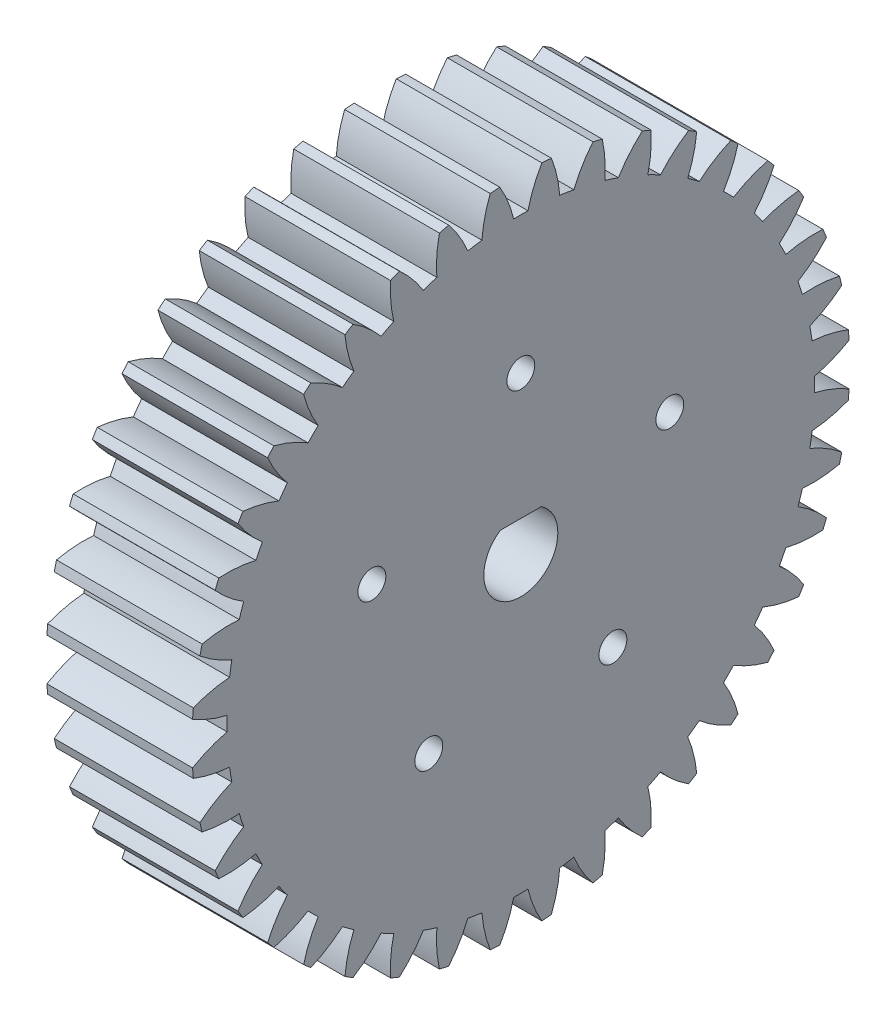
SolidWorks part; units mm, degrees
ref_plane "Plane1" through (0, 0, 0) normal (0, 0, 1) x (1, 0, 0)
ref_plane "Plane2" through (0, 0, 0) normal (0, 1, 0) x (1, 0, 0)
ref_plane "Plane3" through (0, 0, 0) normal (1, 0, 0) x (0, 0, -1)
sketch "HoldingSke" plane through (0, 0, 0) normal (0, 1, 0) x (1, 0, 0)
  line L0 (0, 0) -> (389.1506, -326.5361)
  line L1 (-15, 0) -> (100, 0) construction
  line L2 (0, 0) -> (-2.1039, 2.3779)
  line L3 (0, 0) -> (-11.863, 4.5341)
  line L4 (0, 0) -> (6.6156, 5.5511)
  line L5 (0, 0) -> (-47.5972, -17.7524)
  line L6 (0, 0) -> (-9.7909, -6.6059)
  line L7 (-2.1039, 2.3779) -> (8.8308, 51.9871)
  line L8 (-76.2, 54.61) -> (-75.184, 54.61)
  line L9 (-71.009, 38.7566) -> (-53.1078, 45.2721)
  line L10 (-76.2, 71.12) -> (104.1128, 71.12)
  line L11 (0, 0) -> (-11.811, 0)
  line L12 (-76.2, 101.6) -> (-76.1492, 101.6)
  line L13 (24.9733, 27.94) -> (52.9518, 28.4284)
  line L14 (24.9733, 27.94) -> (25.0241, 27.9398)
  line L15 (24.9733, 27.94) -> (100.4021, 29.52)
  circle A0 centre (0, 0) radius 0.3969
  circle A1 centre (0, 0) radius 23.8252
  circle A2 centre (0, 0) radius 38.1
  circle A3 centre (0, 0) radius 0.3969
  dimension "MHD" = 47.6504
  dimension "Hub_dia" = 76.2
  dimension "Bore" = 0.7937
  dimension "MBD" = 0.7937
  dimension "Num_teeth" = 40
  dimension "Pitch_radius" = 180.3128
  dimension "Pitch" = 508
  dimension "Width" = 11.811
  dimension "Overall_len" = 50.8
  dimension "Show_teeth" = 40
  dimension "Thickness" = 11.811
  dimension "OAL" = 50.8001
  dimension "T_dim" = 1.016
  dimension "Ap" = 20
  dimension "H" = 19.05
  dimension "Backlash" = 0.0508
  dimension "Addendum_fac" = 1
  dimension "Dedendum_fac" = 1.2
  dimension "Clearance_fac" = 0.2
  dimension "Dedendum_add" = 0.0508
sketch "BasProSke" plane through (0, 0, 0) normal (0, 1, 0) x (1, 0, 0)
  line L0 (-10, 0) -> (60, 0) construction
  line L1 (0, 0) -> (0, 26.67)
  line L2 (0, 0) -> (11.811, 0)
  line L3 (11.811, 0) -> (11.811, 26.67)
  line L4 (11.811, 26.67) -> (0, 26.67)
  dimension "Diameter" = 53.34
  dimension "Thickness" = 11.811
revolve "Base-Revolve" add sketch "BasProSke" angle 360 about L0
sketch "TooCutSke" plane through (0, 0, 0) normal (1, 0, 0) x (0, 0, -1)
  line L1 (0, 0) -> (0, 107) construction
  line L2 (0, 0) -> (-1.0861, 25.3768) construction
  line L3 (0, 0) -> (-3.9832, 50.611) construction
  line L4 (-1.0861, 25.3768) -> (-1.9916, 25.3055) construction
  arc A0 (0.5773, 23.8182) -> (-0.5773, 23.8182) centre (0, 0) ccw
  arc A1 (1.7213, 26.6399) -> (-1.7213, 26.6399) centre (0, 0) ccw
  circle A2 centre (0, 0) radius 25.4 construction
  circle A3 centre (0, 0) radius 23.8682 construction
  arc A4 (-0.5773, 23.8182) -> (-1.7213, 26.6399) centre (-10.4586, 21.4548) ccw
  arc A5 (1.7213, 26.6399) -> (0.5773, 23.8182) centre (10.4586, 21.4548) ccw
  dimension "Root_dia" = 47.6504
  dimension "Overcut_dia" = 53.3908
  dimension "Pitch_dia" = 50.8
  dimension "Base_dia" = 47.7364
  dimension "Flank_rad" = 10.16
  dimension "Half_ang" = 4.5
  dimension "Half_CT" = 0.9083
extrude "ToothCut" cut sketch "TooCutSke" along normal through all
fillet "Breaks" [suppressed] radius 0.0254 tangent propagation no
fillet "RootFillets" [suppressed] radius 0.3048
pattern_circular "TeethCuts" count 40 every 9 about axis through (-10, 0, 0) along (1, 0, 0) of "ToothCut", "RootFillets", "Breaks"
sketch "HubNeaOneSke" plane through (0, 0, 0) normal (-1, 0, 0) x (0, 0, 1)
  circle A0 centre (0, 0) radius 23.8252
  dimension "Diameter" = 47.6504
extrude "HubNearOne" [suppressed] add sketch "HubNeaOneSke" along normal blind 38.9891
sketch "HubNeaBotSke" plane through (0, 0, 0) normal (-1, 0, 0) x (0, 0, 1)
  circle A0 centre (0, 0) radius 23.8252
  dimension "Diameter" = 47.6504
extrude "HubNearBoth" [suppressed] add sketch "HubNeaBotSke" along normal blind 19.4945
ref_plane "FarPln" through (11.811, 0, 0) normal (1, 0, 0) x (0, 0, -1)
sketch "HubFarSke" plane through (11.811, 0, 0) normal (1, 0, 0) x (0, 0, -1)
  circle A0 centre (0, 0) radius 23.8252
  dimension "Diameter" = 47.6504
extrude "HubFar" [suppressed] add sketch "HubFarSke" along normal blind 19.4945
sketch "BorSke" plane through (0, 0, 0) normal (1, 0, 0) x (0, 0, -1)
  circle A0 centre (0, 0) radius 0.3969
  dimension "Diameter" = 0.7937
extrude "Bore" cut sketch "BorSke" along normal mid plane 101.6001
sketch "KeySke" plane through (0, 0, 0) normal (1, 0, 0) x (0, 0, -1)
  line L0 (-0.127, 0) -> (-0.127, 0.6191)
  line L1 (-0.127, 0.6191) -> (0.127, 0.6191)
  line L2 (0.127, 0.6191) -> (0.127, 0)
  line L3 (0, 0) -> (0, 34) construction
  line L4 (-0.127, 0) -> (0.127, 0)
  dimension "Offset" = 0.6191
  dimension "Width" = 0.254
extrude "Keyway" [suppressed] cut sketch "KeySke" along normal mid plane 101.6001
pattern_circular "Keyway2" [suppressed] count 2 every 90 about axis through (-10, 0, 0) along (1, 0, 0)
sketch "Sketch3" plane through (11.811, 0, 0) normal (1, 0, 0) x (0, 0, -1)
  line L0 (-1.6583, 2.5) -> (1.6583, 2.5)
  line L1 (0, 0) -> (0, 32.5169) construction
  arc A0 (-1.6583, 2.5) -> (1.6583, 2.5) centre (0, 0) ccw
  circle A1 centre (0, 12.7) radius 1.1303
  circle A2 centre (12.0784, 3.9245) radius 1.1303
  circle A3 centre (7.4649, -10.2745) radius 1.1303
  circle A4 centre (-7.4649, -10.2745) radius 1.1303
  circle A5 centre (-12.0784, 3.9245) radius 1.1303
  point P18 (0, 0)
  dimension "D1" = 6
  dimension "D3" = 2.2606
  dimension "D2" = 2.5
  dimension "D4" = 12.7
  dimension "D5" = 5
extrude "Cut-Extrude1" cut sketch "Sketch3" against normal blind 15.748
equation "' \"Pitch@HoldingSke\" = 4"
equation "' \"Num_teeth@HoldingSke\" = 12"
equation "' \"Ap@HoldingSke\" =  20"
equation "' \"Width@HoldingSke\" = 0.5"
equation "' \"Hub_dia@HoldingSke\"= 1"
equation "' \"Overall_len@HoldingSke\" = 1.0"
equation "' \"Bore@HoldingSke\" = 0.75"
equation "' \"T_dim@HoldingSke\" = 0.85"
equation "' \"Width@KeySke\" = 0.25"
equation "' \"Show_teeth@HoldingSke\" = 13"
equation "' \"Backlash@HoldingSke\" = 0.009"
equation "' \"Addendum_fac@HoldingSke\" = 1.0"
equation "' \"Dedendum_fac@HoldingSke\" = 1.25"
equation "' \"Dedendum_add@HoldingSke\" = 0.00005"
equation "' \"Clearance_fac@HoldingSke\" = 0.25"
equation "' \"Pitch@HoldingSke\" = 0.5"
equation "' \"Num_teeth@HoldingSke\" = 23"
equation "' \"Show_teeth@HoldingSke\" = 23"
equation "' \"Backlash@HoldingSke\" = 0.0375"
equation "\"Overcut_dia@TooCutSke\" = (\"Num_teeth@HoldingSke\" + 2 * \"Addendum_fac@HoldingSke\") / \"Pitch@HoldingSke\" + 0.002"
equation "\"Pitch_dia@TooCutSke\" = \"Num_teeth@HoldingSke\" / \"Pitch@HoldingSke\""
equation "\"Base_dia@TooCutSke\" = \"Num_teeth@HoldingSke\" / \"Pitch@HoldingSke\" * cos((\"Ap@HoldingSke\"  * 3.14159265 / 180))"
equation "\"Root_dia@TooCutSke\" = (\"Num_teeth@HoldingSke\" + 2) / \"Pitch@HoldingSke\" - 2 * (\"Addendum_fac@HoldingSke\" + \"Dedendum_fac@HoldingSke\") / \"Pitch@HoldingSke\" - \"Dedendum_add@HoldingSke\" * 2"
equation "\"Half_ang@TooCutSke\" = 180 / \"Num_teeth@HoldingSke\""
equation "\"Half_CT@TooCutSke\" = \"Num_teeth@HoldingSke\" / \"Pitch@HoldingSke\" * sin((3.14159265 / 2 / \"Num_teeth@HoldingSke\")) / 2 - 7 * \"Backlash@HoldingSke\" / 4"
equation "\"Flank_rad@TooCutSke\" = \"Num_teeth@HoldingSke\" / \"Pitch@HoldingSke\" / 5"
equation "\"Radius@RootFillets\" = \"Clearance_fac@HoldingSke\" / \"Pitch@HoldingSke\" + \"Dedendum_add@HoldingSke\""
equation "\"Break_rad@Breaks\" = 0.02 / \"Pitch@HoldingSke\""
equation "\"Thickness@HoldingSke\" = \"Width@HoldingSke\""
equation "\"OAL@HoldingSke\" = \"Thickness@HoldingSke\""
equation "\"MHD@HoldingSke\" = (\"Num_teeth@HoldingSke\" + 2) / \"Pitch@HoldingSke\" - 2 * (\"Addendum_fac@HoldingSke\" + \"Dedendum_fac@HoldingSke\")  / \"Pitch@HoldingSke\" - \"Dedendum_add@HoldingSke\" * 2"
equation "\"MBD@HoldingSke\" = (\"Num_teeth@HoldingSke\" + 2) / \"Pitch@HoldingSke\" - 2 * (\"Addendum_fac@HoldingSke\" + \"Dedendum_fac@HoldingSke\")  / \"Pitch@HoldingSke\" - \"Dedendum_add@HoldingSke\" * 2 - 0.002"
equation "\"MHD@HoldingSke\" = ((sgn( \"MHD@HoldingSke\" - \"Hub_dia@HoldingSke\" )-1)*( \"MHD@HoldingSke\" - \"Hub_dia@HoldingSke\" ))/-2+ \"Hub_dia@HoldingSke\""
equation "\"MBD@HoldingSke\" = ((sgn( \"MBD@HoldingSke\" - \"Bore@HoldingSke\" )-1)*( \"MBD@HoldingSke\" - \"Bore@HoldingSke\" ))/-2+ \"Bore@HoldingSke\""
equation "\"OAL@HoldingSke\" = ((sgn( \"OAL@HoldingSke\" - \"Overall_len@HoldingSke\" )+1)*( \"OAL@HoldingSke\" - \"Overall_len@HoldingSke\" ))/2 + \"Overall_len@HoldingSke\" + 0.000002"
equation "\"Num_teeth@TeethCuts\" = int( \"Show_teeth@HoldingSke\" ) + 1"
equation "\"Num_teeth@TeethCuts\" = ((sgn( \"Num_teeth@TeethCuts\" - \"Num_teeth@HoldingSke\" )-1)*( \"Num_teeth@TeethCuts\" - \"Num_teeth@HoldingSke\" ))/-2+ \"Num_teeth@HoldingSke\""
equation "\"Num_teeth@TeethCuts\" = ((sgn( \"Num_teeth@TeethCuts\" - 2.0)+1)*( \"Num_teeth@TeethCuts\" - 2.0))/2 +2.0"
equation "\"Angle@TeethCuts\" = 360.0 / \"Num_teeth@HoldingSke\""
equation "\"Diameter@BasProSke\" = (\"Num_teeth@HoldingSke\" + 2 * \"Addendum_fac@HoldingSke\") / \"Pitch@HoldingSke\""
equation "\"Thickness@BasProSke\"  = \"Thickness@HoldingSke\""
equation "' \"Fillet_rad@BasProSke\" =  \"Thickness@HoldingSke\" * 0.05"
equation "\"MHD@HoldingSke\" = ((sgn( \"MHD@HoldingSke\" - \"Root_dia@TooCutSke\" )-1)*( \"MHD@HoldingSke\" - \"Root_dia@TooCutSke\" ))/-2+ \"Root_dia@TooCutSke\""
equation "\"Diameter@HubNeaOneSke\" = \"MHD@HoldingSke\""
equation "\"Length@HubNearOne\" = \"OAL@HoldingSke\" - \"Thickness@BasProSke\""
equation "\"Diameter@HubNeaBotSke\" = \"MHD@HoldingSke\""
equation "\"Length@HubNearBoth\" = ( \"OAL@HoldingSke\" - \"Thickness@BasProSke\" ) / 2.0"
equation "\"Thickness@FarPln\" = \"Thickness@BasProSke\""
equation "\"Diameter@HubFarSke\" = \"MHD@HoldingSke\""
equation "\"Length@HubFar\" = ( \"OAL@HoldingSke\" - \"Thickness@BasProSke\" ) / 2.0"
equation "\"Diameter@BorSke\" = \"MBD@HoldingSke\""
equation "\"D1@Bore\" = \"OAL@HoldingSke\" * 2.0"
equation "\"D1@Keyway\" = \"OAL@HoldingSke\" * 2.0"
equation "\"Offset@KeySke\" = \"T_dim@HoldingSke\" - \"MBD@HoldingSke\" / 2.0"
